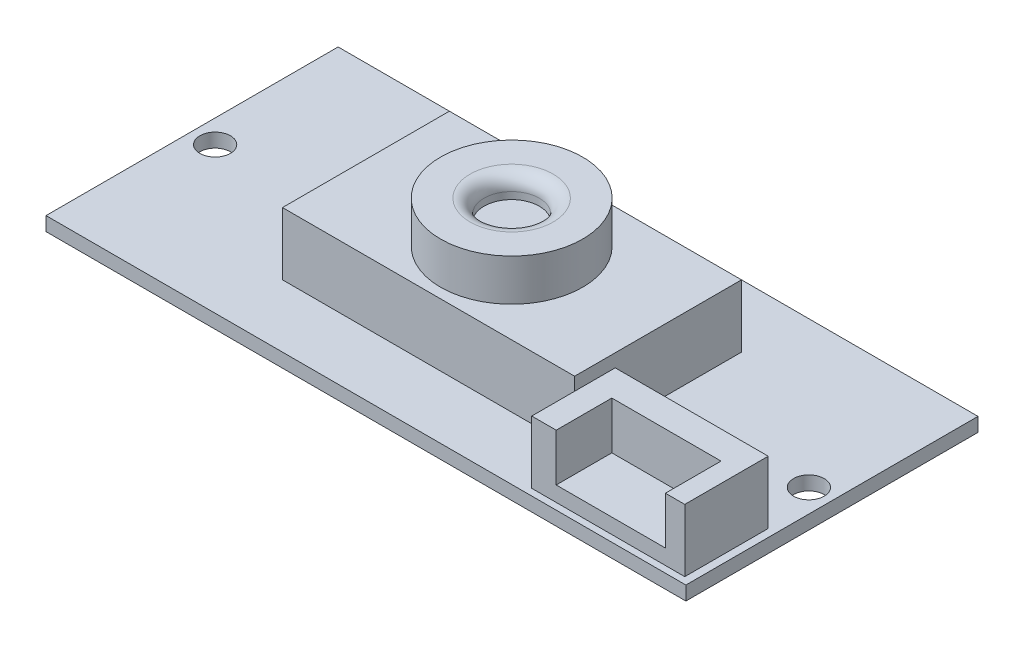
SolidWorks part; units mm, degrees
ref_plane "Front Plane" through (0, 0, 0) normal (0, 0, 1) x (1, 0, 0)
ref_plane "Top Plane" through (0, 0, 0) normal (0, 1, 0) x (1, 0, 0)
ref_plane "Right Plane" through (0, 0, 0) normal (1, 0, 0) x (0, 0, -1)
sketch "Sketch1" plane through (0, 0, 0) normal (0, 1, 0) x (1, 0, 0)
  line L1 (0, 0) -> (46, 0)
  line L2 (0, 0) -> (0, -21)
  line L3 (0, -21) -> (46, -21)
  line L4 (46, 0) -> (46, -21)
  dimension "D1" = 46
  dimension "D2" = 21
extrude "Boss-Extrude1" add sketch "Sketch1" along normal blind 1
sketch "Sketch2" plane through (0, 1, 0) normal (0, 1, 0) x (1, 0, 0)
  line L0 (23, -4.5) -> (23, 0) construction
  line L1 (12.5, -4.5) -> (33.5, -4.5)
  line L2 (12.5, -4.5) -> (12.5, -16.5)
  line L3 (12.5, -16.5) -> (33.5, -16.5)
  line L4 (33.5, -4.5) -> (33.5, -16.5)
  line L5 (46, 0) -> (0, 0) construction
  line L6 (33.5, -10.5) -> (46, -10.5) construction
  line L7 (46, -21) -> (46, 0) construction
  line L8 (23, -16.5) -> (23, -21) construction
  line L9 (0, -21) -> (46, -21) construction
  line L10 (12.5, -10.5) -> (0, -10.5) construction
  line L11 (0, 0) -> (0, -21) construction
  line L13 (34.4396, -14.5205) -> (45.4396, -14.5205)
  line L14 (34.4396, -14.5205) -> (34.4396, -20.5205)
  line L15 (34.4396, -20.5205) -> (45.4396, -20.5205)
  line L16 (45.4396, -14.5205) -> (45.4396, -20.5205)
  point P26 (0, 0)
  point P27 (34.4396, -14.5205)
  dimension "D1" = 21
  dimension "D2" = 12
  dimension "D3" = 11
  dimension "D4" = 6
extrude "Boss-Extrude2" add sketch "Sketch2" along normal blind 4.5
sketch "Sketch3" plane through (0, 0, 20.5205) normal (0, 0, 1) x (1, 0, 0)
  line L0 (34.4396, 5.5) -> (45.4396, 5.5) construction
  line L1 (36.1976, 5.5) -> (44.0475, 5.5)
  line L2 (36.1976, 5.5) -> (36.1976, 2.0877)
  line L3 (36.1976, 2.0877) -> (44.0475, 2.0877)
  line L4 (44.0475, 5.5) -> (44.0475, 2.0877)
extrude "Cut-Extrude1" cut sketch "Sketch3" against normal blind 4
sketch "Sketch4" plane through (0, 5.5, 0) normal (0, 1, 0) x (1, 0, 0)
  circle A0 centre (23.1472, -10.6717) radius 5.1093
  point P2 (23.0981, -10.4264)
  point P3 (0, 0)
  point P4 (23.1472, -10.6717)
extrude "Boss-Extrude3" add sketch "Sketch4" along normal blind 3
sketch "Sketch5" plane through (0, 8.5, 0) normal (0, 1, 0) x (1, 0, 0)
  circle A0 centre (23.1472, -10.6717) radius 1.9868
extrude "Cut-Extrude2" cut sketch "Sketch5" against normal blind 1.5
fillet "Fillet1" radius 1 1 edges at (23.1472, 8.5, 12.6586)
sketch "Sketch6" plane through (0, 1, 0) normal (0, 1, 0) x (1, 0, 0)
  line L0 (1.6582, -21) -> (1.6582, 0) construction
  line L1 (0, -21) -> (46, -21) construction
  line L2 (46, 0) -> (0, 0) construction
  line L3 (44.3418, 0) -> (44.3418, -21) construction
  circle A1 centre (1.6582, -10.5) radius 1.1
  circle A2 centre (44.3418, -10.5) radius 1.1
  point P12 (44.3418, -10.5)
  dimension "D1" = 2.2
  dimension "D2" = 2.2
extrude "Cut-Extrude3" cut sketch "Sketch6" against normal blind 1.5
